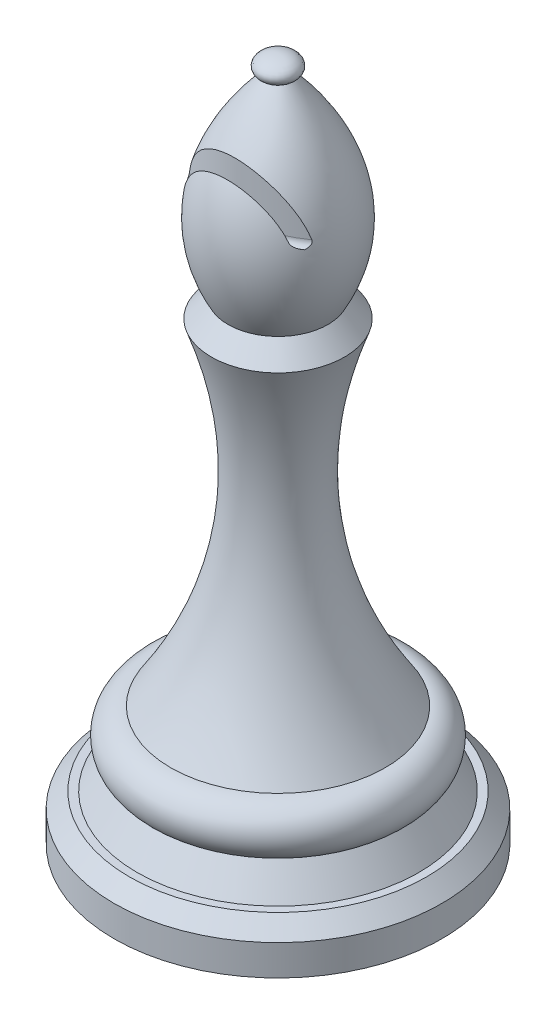
SolidWorks part; units mm, degrees
ref_plane "Front Plane" through (0, 0, 0) normal (0, 0, 1) x (1, 0, 0)
ref_plane "Top Plane" through (0, 0, 0) normal (0, 1, 0) x (1, 0, 0)
ref_plane "Right Plane" through (0, 0, 0) normal (1, 0, 0) x (0, 0, -1)
sketch "Sketch1" plane through (0, 0, 0) normal (0, 1, 0) x (1, 0, 0)
  circle A0 centre (0, 0) radius 13.589
  dimension "D1" = 27.178
extrude "Boss-Extrude1" add sketch "Sketch1" along normal mid plane 3.81
chamfer "Chamfer1" distance 1.27 angle 45 1 edges at (0, 1.905, 13.589)
sketch "Sketch3" plane through (0, 0, 0) normal (1, 0, 0) x (0, 0, -1)
  line L0 (0, -1.905) -> (0, 53.975) construction
  line L1 (-13.589, -1.905) -> (13.589, -1.905) construction
  line L2 (0, 1.905) -> (-11.684, 1.905)
  line L3 (12.319, 1.905) -> (-12.319, 1.905) construction
  line L4 (-5.5231, 35.8228) -> (-4.1438, 37.465)
  line L5 (-4.1438, 37.465) -> (0, 37.465) construction
  line L6 (0, 37.465) -> (0, 1.905)
  line L7 (0, 53.975) -> (0, 55.0937) construction
  line L8 (0, 37.465) -> (0, 54.8454)
  arc A0 (-8.89, 8.0231) -> (-10.16, 4.2662) centre (-8.89, 5.93) ccw
  ellipse E0 centre (0, 53.975) end of major axis (-1.5771, 53.975) minor radius 0.8704 (0, 54.8454) -> (-0.9991, 53.3016) ccw
  spline S0 degree 3 poles (-4.1438, 37.465) (-7.0013, 42.6388) (-5.7179, 48.1293) (-0.9991, 53.3016) knots 0 0 0 0 0.987968 0.987968 0.987968 0.987968
  spline S1 degree 1 poles (-11.684, 1.905) (-10.16, 4.2662) knots 0 0 1 1
  spline S2 degree 2 poles (-8.89, 8.0231) (-0.1896, 21.2061) (-5.5231, 35.8228) knots 0 0 0 1 1 1
  dimension "D1" = 55.88
  dimension "D2" = 1.905
  dimension "D3" = 8.89
  dimension "D4" = 35.56
  dimension "D5" = 10.16
revolve "Revolve1" add sketch "Sketch3" angle 360 about axis through (0, 1.905, 0) along (0, -1, 0)
ref_plane "Plane1" through (0, 44.45, 0) normal (0, 1, 0) x (1, 0, 0)
sketch "Sketch4" plane through (0, 44.45, 0) normal (0, 1, 0) x (1, 0, 0)
  line L0 (-7.9337, -0.3565) -> (-7.4082, 0)
  line L1 (7.6795, -0.3565) -> (7.154, 0)
  arc A0 (-7.4082, 0) -> (7.154, 0) centre (-0.1271, 4.9402) ccw
  arc A2 (-7.9337, -0.3565) -> (7.6795, -0.3565) centre (-0.1271, 4.9402) ccw
  dimension "D1" = 0.635
extrude "Cut-Extrude1" cut sketch "Sketch4" along normal through all
fillet "Fillet1" radius 0.635 2 edges at (0.1155, 44.45, 4.4906) (0.0992, 44.45, 3.8558)
sketch "Sketch5" plane through (0, -1.905, 0) normal (0, -1, 0) x (1, 0, 0)
  circle A0 centre (0, 0) radius 5.0165
  dimension "D1" = 10.033
extrude "Cut-Extrude2" cut sketch "Sketch5" against normal blind 2.54 from offset 0.6 offset against normal yes
